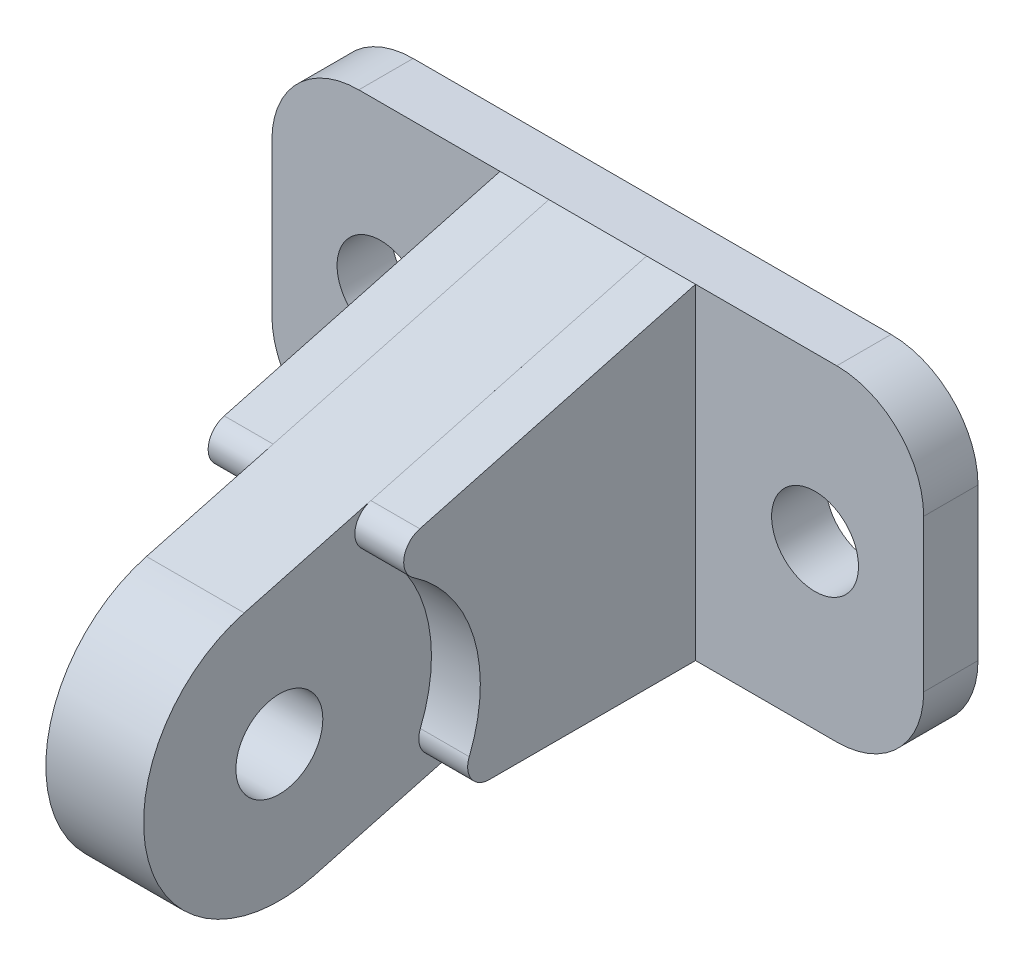
SolidWorks part; units mm, degrees
ref_plane "Front Plane" through (0, 0, 0) normal (0, 0, 1) x (1, 0, 0)
ref_plane "Top Plane" through (0, 0, 0) normal (0, 1, 0) x (1, 0, 0)
ref_plane "Right Plane" through (0, 0, 0) normal (1, 0, 0) x (0, 0, -1)
sketch "Sketch1" plane through (0, 0, 0) normal (0, 0, 1) x (1, 0, 0)
  line L0 (30, 0) -> (0, 0) construction
  line L1 (-22, -15) -> (22, -15)
  line L2 (-30, -7) -> (-30, 7)
  line L3 (-22, 15) -> (22, 15)
  line L4 (30, -7) -> (30, 7)
  line L5 (-30, -15) -> (30, 15) construction
  line L6 (-30, 15) -> (30, -15) construction
  line L7 (0, 0) -> (-30, 0) construction
  line L8 (0, 15) -> (0, -15) construction
  line L14 (-9, -15) -> (9, 15) construction
  line L15 (-9, 15) -> (9, -15) construction
  circle A2 centre (-20, 0) radius 4
  circle A3 centre (20, 0) radius 4
  arc A4 (22, 15) -> (30, 7) centre (22, 7) cw
  arc A5 (22, -15) -> (30, -7) centre (22, -7) ccw
  arc A6 (-22, -15) -> (-30, -7) centre (-22, -7) cw
  arc A7 (-30, 7) -> (-22, 15) centre (-22, 7) cw
  point P0 (0, 0)
  point P11 (0, 0)
  dimension "D3" = 40
  dimension "D5" = 8
  dimension "D1" = 60
  dimension "D2" = 30
  dimension "D4" = 18
extrude "Boss-Extrude1" add sketch "Sketch1" along normal blind 5 contours L1 L3 L2 A2 | L1 L3 | L1 L4 L3 A3 region at (0, 0, 0)
sketch "Sketch3" plane through (0, 0, 0) normal (1, 0, 0) x (0, 0, -1)
  line L0 (-5, 15) -> (-24.3016, 15) construction
  line L1 (-5, 15) -> (-30.3848, 8.1982)
  line L2 (-5, -7) -> (-35.9757, -7) construction
  line L3 (-35.5765, -19.0741) -> (-20.3719, -15)
  line L4 (-42.0468, 5.0741) -> (-5, 15)
  line L5 (-5, -15) -> (-23.9794, -15)
  line L7 (-5, 15) -> (-5, -15)
  circle A0 centre (-38.8118, -7) radius 4
  arc A1 (-25.8334, -12.25) -> (-30.9853, 4.608) centre (-38.8118, -7) ccw
  arc A2 (-42.0468, 5.0741) -> (-35.5765, -19.0741) centre (-38.8118, -7) ccw
  arc A3 (-23.9794, -15) -> (-25.8334, -12.25) centre (-23.9794, -13) cw
  arc A4 (-30.9853, 4.608) -> (-30.3848, 8.1982) centre (-29.8672, 6.2663) cw
  dimension "D2" = 25
  dimension "D3" = 28
  dimension "D4" = 8
  dimension "D5" = 2
  dimension "D1" = 15
extrude "Boss-Extrude2" add sketch "Sketch3" along normal blind 9 and the other way blind 9 contours A4 A1 A3 L5 L7 L1 region at (0, -0.8667, 15.7225)
extrude "Boss-Extrude3" add sketch "Sketch3<3>" along normal blind 4.5 and the other way blind 4.5 contours A1 A4 L1 L4 A2 L3 L5 A3 A0 region at (0, 6.6915, 32.4094)
sketch "Sketch3<3>" plane through (0, 0, 0) normal (1, 0, 0) x (0, 0, -1) same geometry as "Sketch3"
